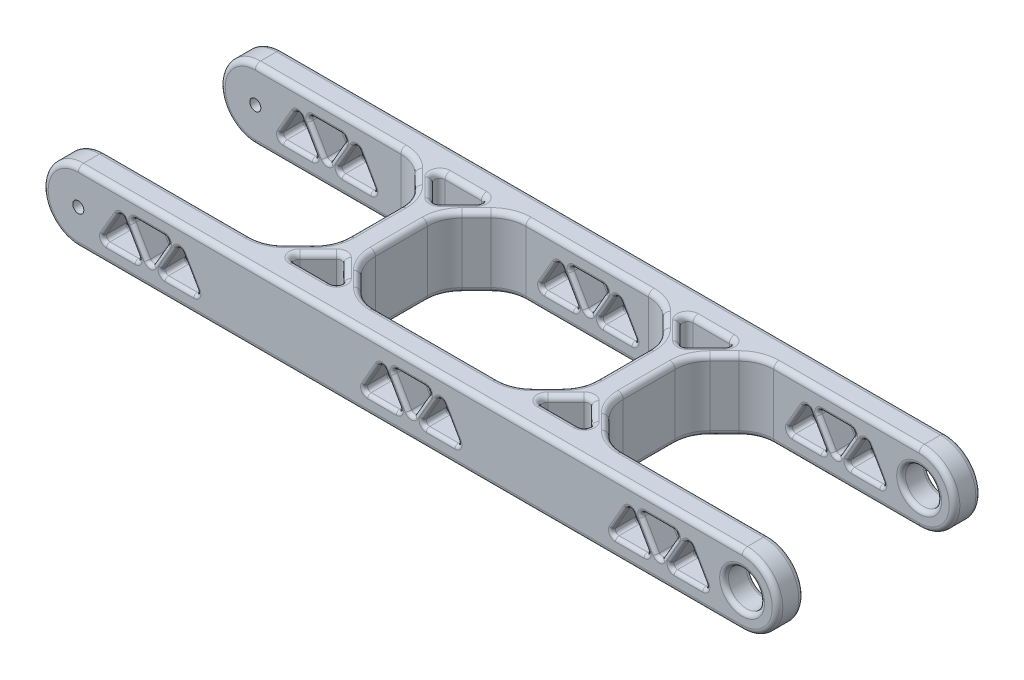
SolidWorks part; units mm, degrees
ref_plane "Front Plane" through (0, 0, 0) normal (0, 0, 1) x (1, 0, 0)
ref_plane "Top Plane" through (0, 0, 0) normal (0, 1, 0) x (1, 0, 0)
ref_plane "Right Plane" through (0, 0, 0) normal (1, 0, 0) x (0, 0, -1)
sketch "Sketch1" plane through (0, 0, 0) normal (0, 0, 1) x (1, 0, 0)
  line L0 (190.5, 10.16) -> (0, 10.16)
  line L1 (190.5, -10.16) -> (0, -10.16)
  arc A0 (0, 10.16) -> (0, -10.16) centre (0, 0) ccw
  circle A1 centre (0, 0) radius 1.5875
  arc A2 (190.5, -10.16) -> (190.5, 10.16) centre (190.5, 0) ccw
  circle A3 centre (190.5, 0) radius 5.1816
  dimension "D1" = 3.175
  dimension "D2" = 20.32
  dimension "D4" = 190.5
  dimension "D3" = 10.3632
extrude "Boss-Extrude1" add sketch "Sketch1" along normal blind 7.62
ref_plane "Plane1" through (0, 0, 50.8) normal (0, 0, 1) x (1, 0, 0)
sketch "Sketch2" plane through (0, 0, 50.8) normal (0, 0, 1) x (1, 0, 0)
  line L0 (190.5, 10.16) -> (0, 10.16)
  line L1 (190.5, -10.16) -> (0, -10.16)
  arc A0 (0, 10.16) -> (0, -10.16) centre (0, 0) ccw
  circle A1 centre (0, 0) radius 1.5875
  arc A2 (190.5, -10.16) -> (190.5, 10.16) centre (190.5, 0) ccw
  circle A3 centre (190.5, 0) radius 5.1816
  dimension "D1" = 3.175
  dimension "D2" = 20.32
  dimension "D4" = 190.5
  dimension "D3" = 10.3632
extrude "Boss-Extrude3" add sketch "Sketch2" along normal blind 7.62 separate body
sketch "Sketch4" plane through (0, 10.16, 0) normal (0, 1, 0) x (1, 0, 0)
  line L0 (55.88, -7.62) -> (55.88, -50.8)
  line L1 (190.5, -7.62) -> (0, -7.62) construction
  line L2 (-9.779, -50.8) -> (9.779, -50.8) construction
  line L3 (55.88, -50.8) -> (63.5, -50.8)
  line L4 (63.5, -50.8) -> (63.5, -7.62)
  line L5 (63.5, -7.62) -> (55.88, -7.62)
  line L6 (95.25, -7.62) -> (95.25, 46.6664) construction
  line L7 (95.25, 46.6664) -> (95.25, -71.3945) construction
  line L8 (127, -50.8) -> (127, -7.62)
  line L9 (134.62, -50.8) -> (127, -50.8)
  line L10 (134.62, -7.62) -> (134.62, -50.8)
  line L11 (127, -7.62) -> (134.62, -7.62)
  dimension "D1" = 31.75
  dimension "D2" = 7.62
extrude "Boss-Extrude4" add sketch "Sketch4" against normal blind 20.32
chamfer "Chamfer2" distance 10 angle 45 2 edges at (134.62, 0, 50.8) (134.62, 0, 7.62)
chamfer "Chamfer3" distance 10 angle 45 6 edges at (63.5, 0, 7.62) (63.5, 0, 50.8) (55.88, 0, 50.8) (55.88, 0, 7.62) (127, 0, 7.62) (127, 0, 50.8)
sketch "Sketch5" plane through (0, 10.16, 0) normal (0, 1, 0) x (1, 0, 0)
  line L0 (95.25, 0) -> (95.25, -58.42) construction
  line L1 (190.5, 0) -> (0, 0) construction
  line L2 (55.88, -29.21) -> (188.3774, -29.21) construction
  line L3 (55.88, -17.62) -> (55.88, -40.8) construction
  line L4 (50.8, -7.62) -> (59.69, -16.51)
  line L5 (59.69, -16.51) -> (68.58, -7.62)
  line L6 (68.58, -7.62) -> (50.8, -7.62)
  line L7 (59.69, -41.91) -> (68.58, -50.8)
  line L8 (50.8, -50.8) -> (59.69, -41.91)
  line L9 (68.58, -50.8) -> (50.8, -50.8)
  line L10 (130.81, -16.51) -> (121.92, -7.62)
  line L11 (139.7, -7.62) -> (130.81, -16.51)
  line L12 (121.92, -7.62) -> (139.7, -7.62)
  line L13 (139.7, -50.8) -> (130.81, -41.91)
  line L14 (121.92, -50.8) -> (139.7, -50.8)
  line L15 (130.81, -41.91) -> (121.92, -50.8)
  line L16 (190.5, -58.42) -> (0, -58.42) construction
  point P20 (88.9, -58.42)
  point P23 (52.0612, -16.0719)
  dimension "D1" = 17.78
  dimension "D2" = 35.56
  dimension "D3" = 45
  dimension "D4" = 7.62
extrude "Cut-Extrude1" cut sketch "Sketch5" against normal blind 20.574
fillet "Fillet1" radius 10 1 edges at (127, 0, 17.62)
fillet "Fillet2" radius 10 14 edges at (45.88, 0, 7.62) (55.88, 0, 17.62) (55.88, 0, 40.8) (45.88, 0, 50.8) (73.5, 0, 50.8) (63.5, 0, 40.8) (73.5, 0, 7.62) (63.5, 0, 17.62) (117, 0, 50.8) (144.62, 0, 50.8) (144.62, 0, 7.62) (134.62, 0, 40.8) (134.62, 0, 17.62) (127, 0, 40.8)
fillet "Fillet3" radius 10 1 edges at (117, 0, 7.62)
fillet "Fillet5" radius 1.524 116 edges at (200.66, 0, 50.8) (169.6311, -10.16, 50.8) (144.9353, -10.16, 50.0388) (139.62, -10.16, 45.8) (135.3812, -10.16, 40.4847) (134.62, -10.16, 29.21) (135.3812, -10.16, 17.9353) (139.62, -10.16, 12.62) (144.9353, -10.16, 8.3812) (169.6311, -10.16, 7.62) (200.66, 0, 7.62) (200.66, 0, 58.42) (95.25, -10.16, 58.42) (-10.16, 0, 58.42) (-10.16, 0, 50.8) (20.8689, -10.16, 50.8) (45.5647, -10.16, 50.0388) (50.88, -10.16, 45.8) (55.1188, -10.16, 40.4847) (55.88, -10.16, 29.21) (55.1188, -10.16, 17.9353) (50.88, -10.16, 12.62) (45.5647, -10.16, 8.3812) (20.8689, -10.16, 7.62) (-10.16, 0, 7.62) (200.66, 0, 0) (95.25, -10.16, 0) (-10.16, 0, 0) (169.6311, 10.16, 7.62) (144.9353, 10.16, 8.3812) (139.62, 10.16, 12.62) (135.3812, 10.16, 17.9353) (134.62, 10.16, 29.21) (135.3812, 10.16, 40.4847) (139.62, 10.16, 45.8) (144.9353, 10.16, 50.0388) (169.6311, 10.16, 50.8) (95.25, 10.16, 58.42) (20.8689, 10.16, 50.8) (45.5647, 10.16, 50.0388) (50.88, 10.16, 45.8) (55.1188, 10.16, 40.4847) (55.88, 10.16, 29.21) (55.1188, 10.16, 17.9353) (50.88, 10.16, 12.62) (45.5647, 10.16, 8.3812) (20.8689, 10.16, 7.62) (95.25, 10.16, 0) (73.8153, 10.16, 8.3812) (68.5, 10.16, 12.62) (64.2612, 10.16, 17.9353) (63.5, 10.16, 29.21) (64.2612, 10.16, 40.4847) (68.5, 10.16, 45.8) (73.8153, 10.16, 50.0388) (95.25, 10.16, 50.8) (116.6847, 10.16, 50.0388) (122, 10.16, 45.8) (126.2388, 10.16, 40.4847) (127, 10.16, 29.21) (126.2388, 10.16, 17.9353) (122, 10.16, 12.62) (116.6847, 10.16, 8.3812) (95.25, 10.16, 7.62) (64.135, 10.16, 12.065) (59.69, 10.16, 7.62) (55.245, 10.16, 12.065) (126.365, 10.16, 46.355) (130.81, 10.16, 50.8) (135.255, 10.16, 46.355) (126.365, 10.16, 12.065) (135.255, 10.16, 12.065) (130.81, 10.16, 7.62) (64.135, 10.16, 46.355) (55.245, 10.16, 46.355) (59.69, 10.16, 50.8) (121.92, 0, 7.62) (130.81, 0, 41.91) (59.69, 0, 41.91) (139.7, 0, 7.62) (130.81, 0, 16.51) (121.92, 0, 50.8) (50.8, 0, 50.8) (139.7, 0, 50.8) (68.58, 0, 50.8) (50.8, 0, 7.62) (59.69, 0, 16.51) (68.58, 0, 7.62) (55.245, -10.16, 12.065) (59.69, -10.16, 7.62) (59.69, -10.16, 50.8) (55.245, -10.16, 46.355) (130.81, -10.16, 7.62) (135.255, -10.16, 12.065) (126.365, -10.16, 46.355) (135.255, -10.16, 46.355) (73.8153, -10.16, 50.0388) (68.5, -10.16, 45.8) (64.2612, -10.16, 40.4847) (63.5, -10.16, 29.21) (64.2612, -10.16, 17.9353) (68.5, -10.16, 12.62) (73.8153, -10.16, 8.3812) (95.25, -10.16, 7.62) (116.6847, -10.16, 8.3812) (122, -10.16, 12.62) (126.2388, -10.16, 17.9353) (127, -10.16, 29.21) (126.2388, -10.16, 40.4847) (122, -10.16, 45.8) (116.6847, -10.16, 50.0388) (64.135, -10.16, 12.065) (64.135, -10.16, 46.355) (126.365, -10.16, 12.065) (95.25, -10.16, 50.8) (130.81, -10.16, 50.8)
sketch "Sketch6" plane through (0, 0, 58.42) normal (0, 0, 1) x (1, 0, 0)
  line L0 (0.8546, 5.08) -> (234.8137, 5.08) construction
  line L1 (6.35, -5.08) -> (12.2159, 5.08)
  line L2 (-0.7267, -5.08) -> (233.2325, -5.08) construction
  line L3 (12.2159, 5.08) -> (18.0818, -5.08)
  line L4 (18.0818, -5.08) -> (6.35, -5.08)
  line L5 (34.8935, -5.08) -> (23.1618, -5.08)
  line L6 (29.0276, 5.08) -> (34.8935, -5.08)
  line L7 (23.1618, -5.08) -> (29.0276, 5.08)
  line L8 (95.25, 8.636) -> (95.25, -24.2672) construction
  line L9 (190.5, 8.636) -> (0, 8.636) construction
  circle A0 centre (0, 0) radius 1.5875 construction
  dimension "D5" = 5.08
  dimension "D2" = 60
  dimension "D3" = 60
  dimension "D4" = 5.08
  dimension "D6" = 6.35
  dimension "D7" = 5.08
  dimension "D1" = 2
extrude "Cut-Extrude2" cut sketch "Sketch6" against normal blind 94.234
sketch "Sketch7" plane through (0, 0, 58.42) normal (0, 0, 1) x (1, 0, 0)
  line L0 (12.2159, 5.08) -> (220.847, 5.08) construction
  line L1 (6.35, -5.08) -> (220.847, -5.08) construction
  line L2 (14.7559, 5.08) -> (20.6218, -5.08)
  line L3 (20.6218, -5.08) -> (26.4876, 5.08)
  line L4 (26.4876, 5.08) -> (14.7559, 5.08)
  line L5 (116.5314, 5.08) -> (116.5314, -22.5361) construction
  point P13 (13.1999, 5.08)
  dimension "D1" = 60
  dimension "D2" = 60
  dimension "D3" = 0
  dimension "D4" = 2.54
extrude "Cut-Extrude3" cut sketch "Sketch7" against normal blind 94.234
fillet "Fillet12" radius 1.016 54 edges at (12.2159, 5.08, 54.61) (18.0818, -5.08, 54.61) (6.35, -5.08, 54.61) (14.7559, 5.08, 54.61) (20.6218, -5.08, 54.61) (26.4876, 5.08, 54.61) (23.1618, -5.08, 54.61) (34.8935, -5.08, 54.61) (29.0276, 5.08, 54.61) (12.2159, -5.08, 7.62) (9.2829, 0, 7.62) (17.6888, 0, 7.62) (20.6218, 5.08, 7.62) (31.9606, 0, 7.62) (29.0276, -5.08, 7.62) (31.9606, 0, 0) (29.0276, -5.08, 0) (20.6218, 5.08, 0) (23.5547, 0, 0) (15.1488, 0, 0) (12.2159, -5.08, 0) (12.2159, -5.08, 50.8) (9.2829, 0, 50.8) (17.6888, 0, 50.8) (20.6218, 5.08, 50.8) (29.0276, -5.08, 50.8) (26.0947, 0, 50.8) (12.2159, -5.08, 58.42) (9.2829, 0, 58.42) (17.6888, 0, 58.42) (20.6218, 5.08, 58.42) (31.9606, 0, 58.42) (29.0276, -5.08, 58.42) (15.1488, 0, 7.62) (23.5547, 0, 7.62) (26.0947, 0, 7.62) (26.0947, 0, 0) (17.6888, 0, 0) (9.2829, 0, 0) (6.35, -5.08, 3.81) (23.1618, -5.08, 3.81) (34.8935, -5.08, 3.81) (18.0818, -5.08, 3.81) (14.7559, 5.08, 3.81) (26.4876, 5.08, 3.81) (29.0276, 5.08, 3.81) (12.2159, 5.08, 3.81) (20.6218, -5.08, 3.81) (15.1488, 0, 50.8) (23.5547, 0, 50.8) (31.9606, 0, 50.8) (15.1488, 0, 58.42) (23.5547, 0, 58.42) (26.0947, 0, 58.42)
pattern_linear "LPattern1" count 2 spacing 74.93 along (1, 0, 0) of "Cut-Extrude2", "Cut-Extrude3", "Fillet12"
fillet "Fillet13" radius 1.27 4 edges at (195.6816, 0, 58.42) (195.6816, 0, 50.8) (195.6816, 0, 7.62) (195.6816, 0, 0)
pattern_linear "LPattern2" count 2 spacing 146.05 along (1, 0, 0) of "Cut-Extrude3", "Cut-Extrude2", "Fillet12"
fillet "Fillet14" [suppressed] radius 1.016
fillet "Fillet8" [suppressed] radius 0.762
fillet "Fillet11" [suppressed] radius 0.762
